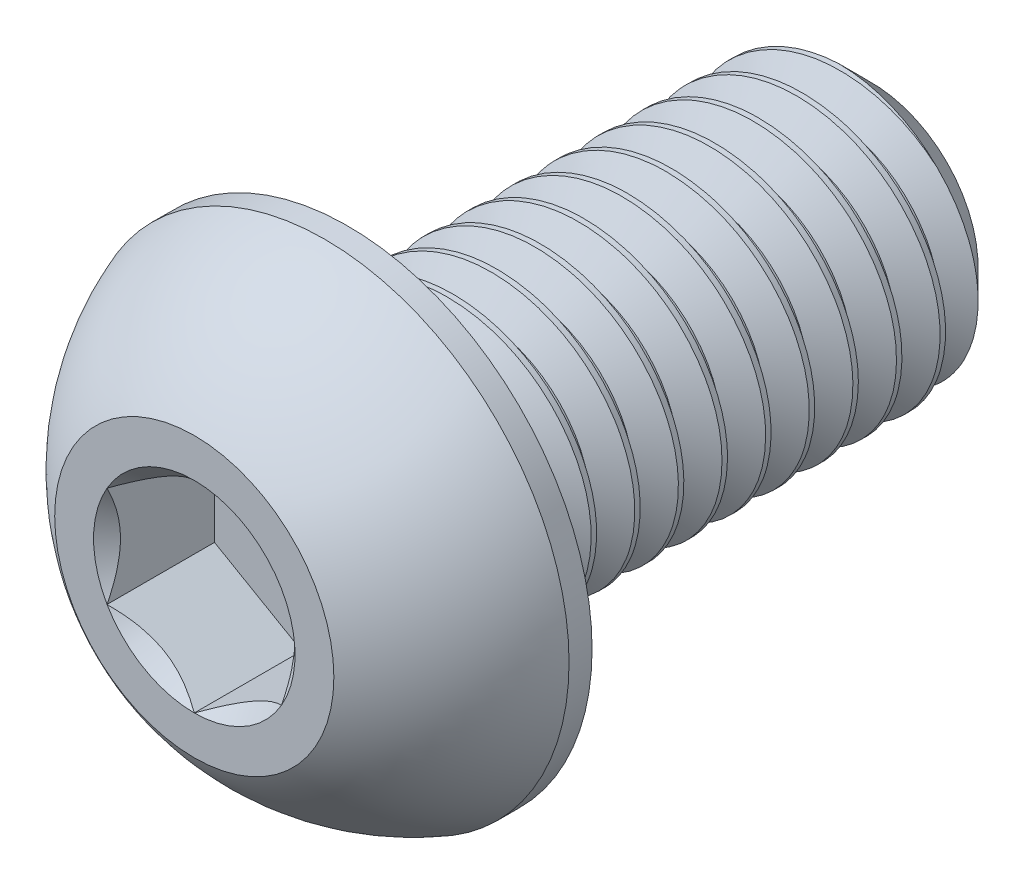
SolidWorks part; units mm, degrees
note: '?' marks a value the reader was unsure of.
ref_plane "Front" through (0, 0, 0) normal (0, 0, 1) x (1, 0, 0)
ref_plane "Top" through (0, 0, 0) normal (0, 1, 0) x (1, 0, 0)
ref_plane "Right" through (0, 0, 0) normal (1, 0, 0) x (0, 0, -1)
sketch "Sketch1" plane through (0, 0, 0) normal (1, 0, 0) x (0, 0, -1)
  line L2 (4.4, 4) -> (19.4, 4)
  line L3 (19.4, 4) -> (19.4, 0)
  line L4 (19.4, 0) -> (4.4, 0)
  line L6 (3.74, 7) -> (4.4, 7) construction
  line L7 (19.4, 4) -> (19.4, -4) construction
  line L8 (0, 0) -> (4.4, 0) construction
  line L9 (4.4, 7) -> (4.4, -7) construction
  line L11 (4.4, 4) -> (4.4, 0)
  line L13 (0, 2.5) -> (0, -2.5) construction
  line L14 (0, 2.5) -> (0, 4) construction
  arc A3 (0, 4) -> (3.74, 7) centre (6.2818, 0) cw construction
  dimension "D1" = 0.66
revolve "Revolve1" add sketch "Sketch1" angle 360 mid plane about L4
sketch "Sketch3" plane through (0, 0, -19.4) normal (0, 0, -1) x (-1, 0, 0)
  circle A0 centre (0, 0) radius 4
curve "Helix/Spiral1" pitch 1.25 height 16.25 turns 13
chamfer "Chamfer1" distance 0.9375 angle 45 1 edges at (-4, 0, -19.4)
sketch "Sketch7" plane through (0, 0, 0) normal (1, 0, 0) x (0, 0, -1)
  line L6 (3.74, 7) -> (4.4, 7) construction
  line L8 (0, 0) -> (4.4, 0) construction
  line L11 (4.4, 7) -> (4.4, -7) construction
  line L12 (3.74, 7) -> (4.4, 7)
  line L13 (0, 0) -> (4.4, 0)
  line L14 (0, 2.5) -> (0, -2.5) construction
  line L15 (4.4, 7) -> (4.4, 0)
  line L16 (0, 4) -> (0, 0)
  arc A2 (3.74, 7) -> (0, 4) centre (6.2818, 0) ccw construction
  arc A3 (3.74, 7) -> (0, 4) centre (6.2818, 0) ccw
revolve "Revolve2" add sketch "Sketch7" angle 360 mid plane about L13
sketch "Sketch5" plane through (0, 0, 0) normal (0, 0, 1) x (1, 0, 0)
  line L1 (2.5, -1.4434) -> (2.5, 1.4434)
  line L2 (2.5, 1.4434) -> (0, 2.8868)
  line L3 (0, 2.8868) -> (-2.5, 1.4434)
  line L4 (-2.5, 1.4434) -> (-2.5, -1.4434)
  line L5 (-2.5, -1.4434) -> (0, -2.8868)
  line L6 (0, -2.8868) -> (2.5, -1.4434)
  circle A0 centre (0, 0) radius 2.5 construction
extrude "Cut-Extrude2" cut sketch "Sketch5" against normal blind 3.08
sketch "Sketch6" plane through (0, 0, 0) normal (0, 0, 1) x (1, 0, 0)
  circle A0 centre (0, 0) radius 2.8868
extrude "Cut-Extrude3" cut sketch "Sketch6" against normal blind 3.08 draft 45
sketch "Sketch2" plane through (0, 0, 0) normal (1, 0, 0) x (0, 0, -1)
  line L0 (18.4625, 4) -> (19.5562, 4)
  line L1 (19.5562, 4) -> (19.0875, 3.1881)
  line L2 (19.0875, 3.1881) -> (18.9312, 3.1881)
  line L3 (18.9312, 3.1881) -> (18.4625, 4)
  line L4 (18.6969, 3.5941) -> (19.3219, 3.5941) construction
  dimension "D1" = 60
  dimension "D2" = 0.1562
  dimension "D3" = 0.625
sweep "Cut-Sweep1" cut profiles "Sketch2" path "Helix/Spiral1"
sketch "Sketch10" plane through (0, 0, 0) normal (1, 0, 0) x (0, 0, -1)
  line L0 (19.4, 4) -> (19.4, -4) construction
  point P0 (17.525, -4)
  dimension "D1" = 1.875
ref_axis "Center Axis 1" through (0, 0, -8.1113) along (0, 0, 1)?
ref_plane "Contact Plane 1" through (0, 0, -4.4) normal (0, 0, -1) x (-1, 0, 0)
ref_plane "Contact Plane 2" through (0, 0, 0) normal (0, 0, 1) x (1, 0, 0)
equation "\"D3@Helix/Spiral1\" = \"Lg@Sketch1\" + \"D4@Helix/Spiral1\""
equation "\"D2@Sketch2\" = \"D4@Helix/Spiral1\" * .125"
equation "\"D3@Sketch2\" = \"D4@Helix/Spiral1\" * .5"
equation "\"D1@Chamfer1\" = \"D4@Helix/Spiral1\" * .75"
equation "\"D1@Cut-Extrude2\" = \"Head Ht@Sketch1\" * .7"
equation "\"D1@Sketch1\" = \"Head Ht@Sketch1\" * .15"
equation "\"D1@Sketch10\" = \"D4@Helix/Spiral1\" * 1.5"
equation "\"D1@Cut-Extrude3\" = \"D1@Cut-Extrude2\""
